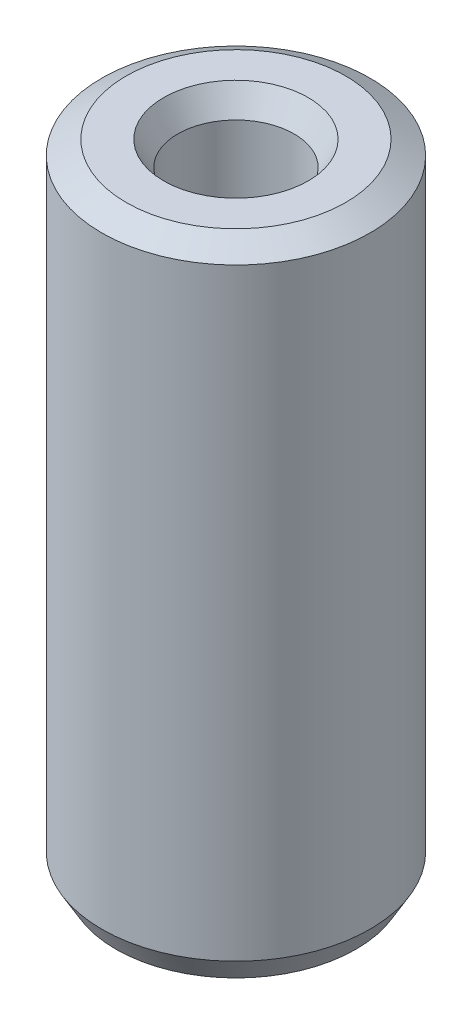
SolidWorks part; units mm, degrees
ref_plane "Front Plane" through (0, 0, 0) normal (0, 0, 1) x (1, 0, 0)
ref_plane "Top Plane" through (0, 0, 0) normal (0, 1, 0) x (1, 0, 0)
ref_plane "Right Plane" through (0, 0, 0) normal (1, 0, 0) x (0, 0, -1)
sketch "Sketch1" plane through (0, 0, 0) normal (0, 1, 0) x (1, 0, 0)
  circle A0 centre (0, 0) radius 5
  dimension "SLEEVE_OD" = 10
extrude "Boss-Extrude1" add sketch "Sketch1" along normal blind 23.913
sketch "Sketch2" plane through (0, 0, 0) normal (0, 1, 0) x (1, 0, 0)
  circle A0 centre (0, 0) radius 2.1678
  dimension "BORE_D" = 4.3356
extrude "Cut-Extrude1" cut sketch "Sketch2" along normal through all
chamfer "Chamfer1" distance 0.5258 angle 60 4 edges at (0, 23.913, 2.1678) (0, 0, 2.1678) (0, 0, 5) (0, 23.913, 5) first distance on face at (0, 23.913, 2.1678) first distance on face at (0, 0, 2.1678) first distance on face at (0, 23.913, 5)
